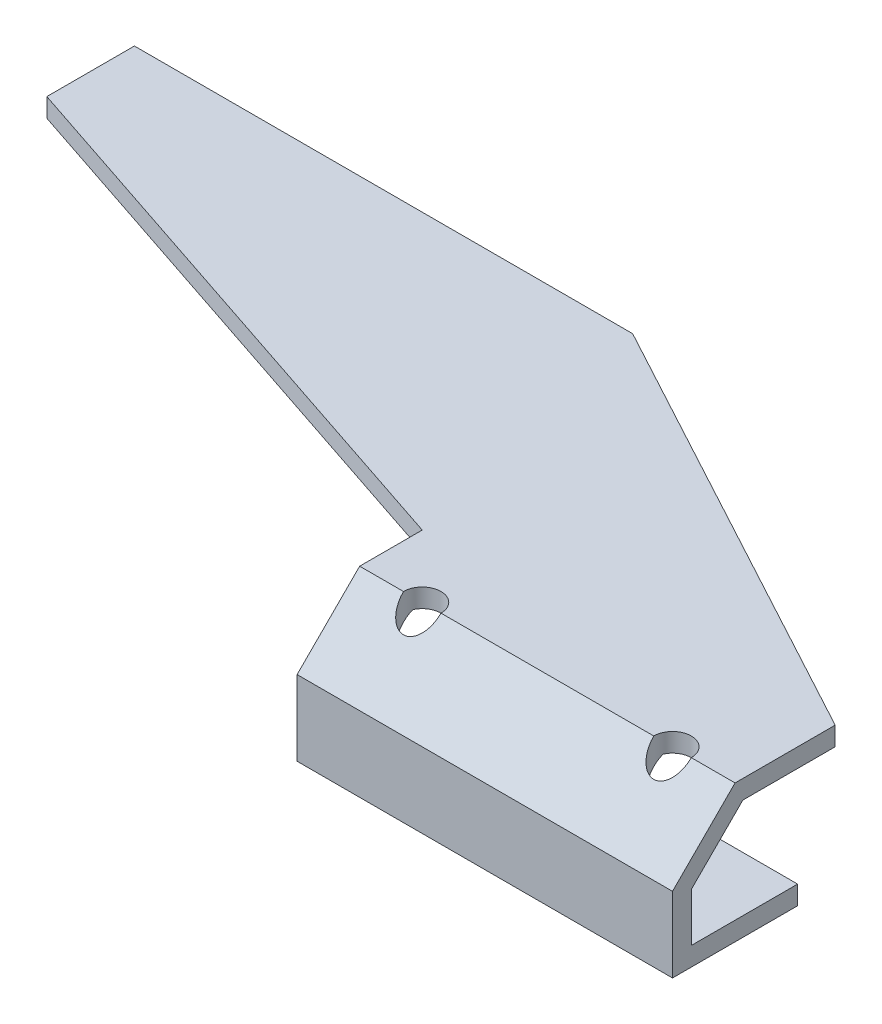
SolidWorks part; units mm, degrees
ref_plane "Top Plane" through (0, 0, 0) normal (0, 0, 1) x (1, 0, 0)
ref_plane "Right Plane" through (0, 0, 0) normal (0, 1, 0) x (1, 0, 0)
ref_plane "Front Plane" through (0, 0, 0) normal (1, 0, 0) x (0, 0, -1)
sketch "Sketch1" plane through (0, 0, 0) normal (1, 0, 0) x (0, 0, -1)
  line L0 (20, 0) -> (0, 0)
  line L1 (0, 0) -> (0, 12)
  line L2 (0, 12) -> (10, 22)
  line L3 (10, 22) -> (64, 22)
  line L4 (64, 22) -> (80, 6)
  line L5 (80, 6) -> (80, -14)
  line L6 (20, 3) -> (3, 3)
  line L7 (3, 3) -> (3, 10.7574)
  line L8 (3, 10.7574) -> (11.2426, 19)
  line L9 (11.2426, 19) -> (62.7574, 19)
  line L10 (62.7574, 19) -> (77, 4.7574)
  line L11 (77, 4.7574) -> (77, -14)
  line L12 (20, 3) -> (20, 0)
  line L13 (77, -14) -> (80, -14)
  dimension "D1" = 10
  dimension "D2" = 16
  dimension "D3" = 20
  dimension "D4" = 80
  dimension "D5" = 10
  dimension "D6" = 20
  dimension "D7" = 12
  dimension "D8" = 3
extrude "Boss-Extrude1" add sketch "Sketch1" against normal blind 150
sketch "Sketch2" plane through (0, 0, 0) normal (0, 1, 0) x (1, 0, 0)
  line L0 (-100, 80) -> (0, 26)
  line L2 (-150, 80) -> (0, 80) construction
  line L3 (0, 64) -> (0, 10) construction
  line L4 (0, 26) -> (0, 80)
  line L5 (0, 80) -> (-100, 80)
  line L6 (-150, 0) -> (-60, 0)
  line L7 (-150, 0) -> (0, 0) construction
  line L8 (-60, 0) -> (-60, 20)
  line L9 (-60, 20) -> (-150, 50)
  line L10 (-150, 64) -> (-150, 10) construction
  line L11 (-150, 50) -> (-150, 0)
  line L12 (-150, 20) -> (0, 20) construction
  line L13 (0, 0) -> (0, 20) construction
  point P18 (0, 0)
  dimension "D1" = 54
  dimension "D2" = 100
  dimension "D3" = 60
  dimension "D4" = 50
extrude "Cut-Extrude5" cut sketch "Sketch2" along normal through all both and the other way through all
sketch "Sketch3" plane through (0, 0, 0) normal (0, -1, 0) x (1, 0, 0)
  line L0 (-60, -10) -> (0, -10) construction
  line L1 (-60, 0) -> (-60, -20) construction
  line L2 (0, 0) -> (0, -20) construction
  line L3 (-30, 0) -> (-30, -20) construction
  line L4 (-60, 0) -> (0, 0) construction
  line L5 (-60, -20) -> (0, -20) construction
  circle A0 centre (-50, -10) radius 1.6
  circle A1 centre (-10, -10) radius 1.6
  point P16 (0, 0)
  dimension "D1" = 3.2
  dimension "D2" = 40
extrude "Cut-Extrude6" cut sketch "Sketch3" against normal up to next
sketch "Sketch4" plane through (0, 3, 0) normal (0, 1, 0) x (1, 0, 0)
  circle A0 centre (-50, 10) radius 3
  circle A1 centre (-50, 10) radius 1.6 construction
  circle A3 centre (-10, 10) radius 3
  point P4 (0, 0)
  point P6 (0, 0)
  dimension "D1" = 6
extrude "Cut-Extrude7" cut sketch "Sketch4" along normal through all
sketch "Sketch5" plane through (0, 0, 0) normal (0, -1, 0) x (1, 0, 0)
  line L0 (-60, -10) -> (0, -10) construction
  line L1 (-60, 0) -> (-60, -20) construction
  line L2 (0, 0) -> (0, -20) construction
  circle A0 centre (-30, -10) radius 5
  point P8 (0, 0)
  dimension "D1" = 10
extrude "Cut-Extrude8" cut sketch "Sketch5" against normal up to next
